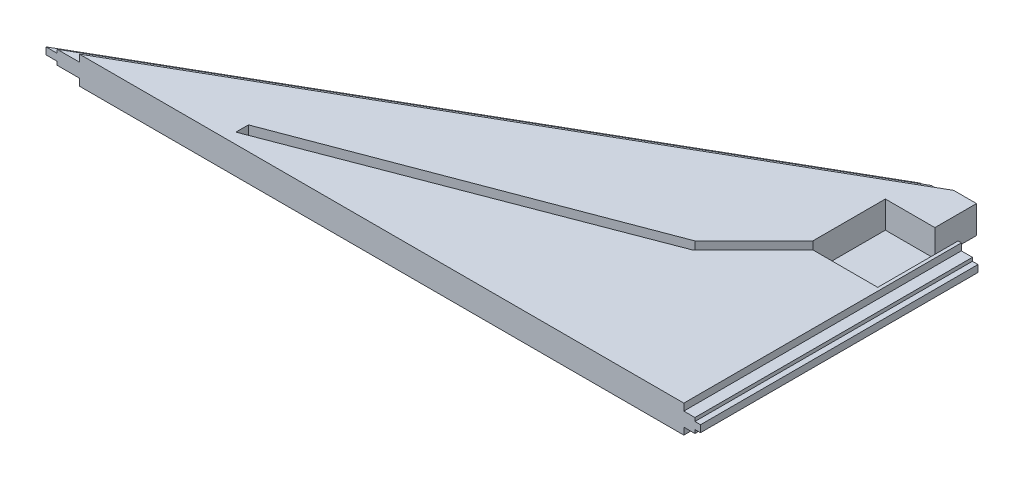
SolidWorks part; units mm, degrees
ref_plane "Front Plane" through (0, 0, 0) normal (0, 0, 1) x (1, 0, 0)
ref_plane "Top Plane" through (0, 0, 0) normal (0, 1, 0) x (1, 0, 0)
ref_plane "Right Plane" through (0, 0, 0) normal (1, 0, 0) x (0, 0, -1)
sketch "Sketch1" plane through (0, 0, 0) normal (0, 1, 0) x (1, 0, 0)
  line L0 (-406.4, 0) -> (0, 0)
  line L1 (0, 0) -> (0, 146.05)
  line L2 (0, 146.05) -> (-152.4, 146.05)
  line L3 (-152.4, 146.05) -> (-406.4, 0)
  dimension "D1" = 406.4
  dimension "D2" = 152.4
  dimension "D3" = 146.05
extrude "Boss-Extrude1" add sketch "Sketch1" along normal blind 6.35 and the other way blind 6.35 contours L3 L0 L1 L2
sketch "Sketch2" plane through (-100.9796, 0, -175.6167) normal (-0.4985, 0, -0.8669) x (-0.8669, 0, 0.4985)
  line L0 (59.3148, 6.35) -> (59.3148, 3.175)
  line L1 (59.3148, -6.35) -> (59.3148, 6.35) construction
  line L2 (59.3148, 3.175) -> (352.3107, 3.175)
  line L3 (352.3107, -6.35) -> (352.3107, 6.35) construction
  line L4 (352.3107, 3.175) -> (352.3107, 6.35)
  line L5 (352.3107, 6.35) -> (59.3148, 6.35)
  line L6 (59.3148, -6.35) -> (59.3148, -3.175)
  line L7 (59.3148, -6.35) -> (352.3107, -6.35)
  line L8 (352.3107, -6.35) -> (352.3107, -3.175)
  line L9 (352.3107, -3.175) -> (59.3148, -3.175)
  dimension "D1" = 3.175
  dimension "D2" = 3.175
extrude "Cut-Extrude1" cut sketch "Sketch2" against normal blind 38.1
sketch "Sketch3" plane through (0, 0, 0) normal (1, 0, 0) x (0, 0, -1)
  line L0 (0, 6.35) -> (0, 3.175)
  line L2 (0, 6.35) -> (146.05, 6.35)
  line L3 (146.05, 6.35) -> (146.05, 3.175)
  line L4 (146.05, -6.35) -> (146.05, 6.35) construction
  line L5 (0, 3.175) -> (146.05, 3.175)
  line L6 (0, -6.35) -> (0, -3.175)
  line L7 (0, -3.175) -> (146.05, -3.175)
  line L8 (146.05, -3.175) -> (146.05, -6.35)
  line L9 (146.05, -6.35) -> (0, -6.35)
  dimension "D1" = 3.175
  dimension "D2" = 3.175
  dimension "D3" = 3.175
  dimension "D4" = 3.175
extrude "Cut-Extrude2" cut sketch "Sketch3" against normal blind 38.1
sketch "Sketch4" plane through (0, 6.35, 0) normal (0, 1, 0) x (1, 0, 0)
  line L0 (-133.4083, 113.0209) -> (-75.9663, 146.05)
  line L1 (-38.1, 146.05) -> (-152.4, 146.05) construction
  line L2 (-75.9663, 146.05) -> (-152.4, 146.05)
  line L3 (-152.4, 146.05) -> (-133.4083, 113.0209)
  line L4 (-329.9663, 0) -> (-133.4083, 113.0209) construction
extrude "Cut-Extrude3" cut sketch "Sketch4" against normal blind 3.175
sketch "Sketch5" plane through (0, -6.35, 0) normal (0, -1, 0) x (1, 0, 0)
  line L0 (-133.4083, -113.0209) -> (-75.9663, -146.05)
  line L1 (-38.1, -146.05) -> (-152.4, -146.05) construction
  line L2 (-75.9663, -146.05) -> (-152.4, -146.05)
  line L3 (-152.4, -146.05) -> (-133.4083, -113.0209)
  line L4 (-329.9663, 0) -> (-133.4083, -113.0209) construction
extrude "Cut-Extrude4" cut sketch "Sketch5" against normal blind 3.175
sketch "Sketch6" plane through (0, 0, -146.05) normal (0, 0, -1) x (-1, 0, 0)
  line L0 (38.1, 6.35) -> (0, 0) construction
  line L1 (0, 0) -> (38.1, -6.35) construction
  line L2 (0, -3.175) -> (0, 3.175) construction
  line L3 (38.622, 3.2182) -> (19.3128, 0) construction
  line L4 (19.3128, 0) -> (38.622, -3.2182) construction
  line L5 (38.1, -3.175) -> (43.18, -3.175)
  line L6 (43.18, -3.175) -> (43.18, -6.35)
  line L7 (38.1, -6.35) -> (75.9663, -6.35) construction
  line L8 (43.18, -6.35) -> (38.1, -6.35)
  line L9 (38.1, 3.175) -> (43.18, 3.175)
  line L10 (43.18, 3.175) -> (43.18, 6.35)
  line L11 (38.1, 6.35) -> (75.9663, 6.35) construction
  line L12 (43.18, 6.35) -> (38.1, 6.35)
  line L13 (38.1, 6.35) -> (0, 6.35)
  line L14 (0, 6.35) -> (0, -6.35)
  line L15 (0, -6.35) -> (38.1, -6.35)
  line L16 (38.1, -3.175) -> (38.1, -1.5875)
  line L22 (38.1, -1.5875) -> (35.56, -1.5875)
  line L23 (35.56, -1.5875) -> (35.56, 1.5875)
  line L24 (35.56, 1.5875) -> (38.1, 1.5875)
  line L25 (38.1, 1.5875) -> (38.1, 3.175)
  line M7 (75.9663, 6.35) -> (38.1, 6.35)
  line M8 (38.1, 6.35) -> (38.1, 3.175)
  line M9 (38.1, 3.175) -> (0, 3.175)
  line M10 (0, 3.175) -> (0, -3.175)
  line M11 (0, -3.175) -> (38.1, -3.175)
  line M12 (38.1, -3.175) -> (38.1, -6.35)
  line M13 (38.1, -6.35) -> (75.9663, -6.35)
  dimension "D2" = 1.5875
  dimension "D1" = 3.175
  dimension "D3" = 5.08
  dimension "D4" = 5.08
  dimension "D5" = 2.54
  dimension "D6" = 3.175
extrude "Cut-Extrude5" cut sketch "Sketch6" against normal blind 157.099 contours L9 L10 M7 M8 | L6 L5 M12 M13 | L4 L3 M11 M9 M10 | L4 L3 region at (-18.4369, 0, -146.05) region at (-40.64, -4.7625, -146.05) region at (-40.64, 4.7625, -146.05)
sketch "Sketch7" plane through (0, -3.175, 0) normal (0, -1, 0) x (1, 0, 0)
  line L0 (-152.4, -146.05) -> (-133.4083, -113.0209) construction
  line L1 (-329.9663, 0) -> (-75.9663, -146.05) construction
  line L2 (-75.9663, -146.05) -> (-329.9663, 0) construction
ref_plane "Plane1" through (-51.4204, 0, 29.5667) normal (-0.8669, 0, 0.4985) x (0.4985, 0, 0.8669)
sketch "Sketch8" plane through (-51.4204, 0, 29.5667) normal (-0.8669, 0, 0.4985) x (0.4985, 0, 0.8669)
  line L0 (-202.5787, 0) -> (-164.4787, 0) construction
  line L1 (-202.5787, -3.175) -> (-202.5787, 3.175) construction
  line L2 (-164.4787, 0) -> (-164.4787, -6.35) construction
  line L3 (-164.4787, -6.35) -> (-202.5787, 0) construction
  line L4 (-202.5787, 0) -> (-164.4787, 6.35) construction
  line L5 (-164.4787, 0) -> (-164.4787, 6.35) construction
  line L6 (-163.9567, -3.2182) -> (-183.2659, 0) construction
  line L7 (-183.2659, 0) -> (-163.9567, 3.2182) construction
  line L8 (-164.4787, 3.175) -> (-159.3987, 3.175)
  line L9 (-159.3987, 3.175) -> (-159.3987, 6.35)
  line L10 (-159.3987, 6.35) -> (-164.4787, 6.35)
  line L11 (-164.4787, -3.175) -> (-159.3987, -3.175)
  line L12 (-159.3987, -3.175) -> (-159.3987, -6.35)
  line L13 (-159.3987, -6.35) -> (-164.4787, -6.35)
  line L14 (-164.4787, 6.35) -> (-202.5787, 6.35)
  line L15 (-202.5787, 6.35) -> (-202.5787, -6.35)
  line L16 (-202.5787, -6.35) -> (-164.4787, -6.35)
  line L17 (-164.4787, -3.175) -> (-164.4787, -1.5875)
  line L23 (-164.4787, -1.5875) -> (-167.0187, -1.5875)
  line L24 (-167.0187, -1.5875) -> (-167.0187, 1.5875)
  line L25 (-167.0187, 1.5875) -> (-164.4787, 1.5875)
  line L26 (-164.4787, 1.5875) -> (-164.4787, 3.175)
  point P7 (-164.4787, -3.175)
  point P11 (-164.4787, 3.175)
  dimension "D5" = 1.5875
  dimension "D1" = 38.1
  dimension "D2" = 6.35
  dimension "D3" = 6.35
  dimension "D6" = 5.08
  dimension "D7" = 3.175
  dimension "D8" = 5.08
  dimension "D9" = 3.175
  dimension "D10" = 38.1
  dimension "D11" = 12.7
  dimension "D12" = 2.54
  dimension "D13" = 3.175
  dimension "D14" = 1.5875
  dimension "D4" = 3.175
extrude "Cut-Extrude6" cut sketch "Sketch8" against normal blind 157.099 and the other way blind 339.217 contours L8 L9 L10 L14 L15 L16 L13 L12 L11 L6 L7 | L7 L6 region at (-142.3615, 0, -128.5917)
sketch "Sketch9" plane through (0, 6.35, 0) normal (0, 1, 0) x (1, 0, 0)
  line L5 (0, 146.05) -> (-50.8, 146.05)
  line L6 (0, 146.05) -> (-152.4, 146.05) construction
  line L7 (-50.8, 146.05) -> (-50.8, 127)
  line L8 (-50.8, 127) -> (0, 127)
  line L9 (0, 0) -> (0, 146.05) construction
  line L10 (0, 146.05) -> (0, 127)
  dimension "D1" = 50.8
  dimension "D2" = 19.05
extrude "Cut-Extrude7" cut sketch "Sketch9" against normal blind 21.59
sketch "Sketch10" plane through (0, 6.35, 0) normal (0, 1, 0) x (1, 0, 0)
  line L0 (-44.68, 127) -> (-44.68, 0) construction
  line L1 (-50.8, 127) -> (-43.18, 127) construction
  line L2 (-319.7751, 0) -> (-43.18, 0) construction
  line L4 (-44.68, 127) -> (-51.765, 127)
  line L5 (-44.68, 127) -> (-44.68, 90.23)
  line L6 (-44.68, 90.23) -> (-51.765, 90.23)
  line L7 (-51.765, 127) -> (-51.765, 90.23)
  line L8 (-51.765, 127) -> (-77.95, 127)
  line L10 (-51.765, 90.23) -> (-77.95, 90.23)
  line L11 (-77.95, 127) -> (-77.95, 90.23)
  line M10 (-43.18, 127) -> (-50.8, 127)
  dimension "D1" = 1.5
  dimension "D2" = 36.77
  dimension "D3" = 7.085
  dimension "D4" = 26.185
extrude "Cut-Extrude9" cut sketch "Sketch10" against normal blind 12.35 contours L8 L11 L10 L7 | L4 L7 L6 L5 M10 region at (-48.2225, 6.35, -108.615) region at (-64.8575, 6.35, -108.615)
sketch "Sketch11" plane through (0, 6.35, 0) normal (0, 1, 0) x (1, 0, 0)
  line L1 (-44.68, 127) -> (-51.765, 127)
  line L2 (-44.68, 127) -> (-44.68, 149.6338)
  line L3 (-44.68, 149.6338) -> (-51.765, 149.6338)
  line L4 (-51.765, 127) -> (-51.765, 149.6338)
  line L5 (-51.765, 127) -> (-55.295, 127)
  line L6 (-51.765, 127) -> (-51.765, 149.6338)
  line L7 (-51.765, 149.6338) -> (-55.295, 149.6338)
  line L8 (-55.295, 127) -> (-55.295, 149.6338)
  line M10 (-77.95, 127) -> (-50.8, 127)
  line M11 (-50.8, 127) -> (-50.8, 146.05)
  line M12 (-50.8, 146.05) -> (-65.7751, 146.05)
  dimension "D1" = 7.085
  dimension "D2" = 3.53
extrude "Cut-Extrude10" cut sketch "Sketch11" against normal through all contours L8 L4 M10 M12 | L4 M10 M11 M12 region at (-51.2825, 6.35, -136.525) region at (-53.53, 6.35, -136.525)
sketch "Sketch12" plane through (0, 6.35, 0) normal (0, 1, 0) x (1, 0, 0)
  line L0 (-77.95, 90.23) -> (-103.35, 64.83)
  line L1 (-44.68, 90.23) -> (-77.95, 90.23) construction
  line L2 (-103.35, 64.83) -> (-253.0681, 7.62)
  line L3 (-319.7751, 0) -> (-43.18, 0) construction
  line L4 (-90.65, 77.53) -> (-88.8539, 75.7339) construction
  line L5 (-90.65, 77.53) -> (-92.4461, 79.3261) construction
  line L6 (-147.0885, 48.1167) -> (-146.1819, 45.744) construction
  line L7 (-147.0885, 48.1167) -> (-147.9952, 50.4894) construction
  line L8 (-88.8539, 75.7339) -> (-101.9371, 62.6508)
  line L9 (-88.8539, 75.7339) -> (-74.3579, 90.23)
  line L10 (-92.4461, 79.3261) -> (-77.95, 93.8221)
  line L11 (-77.95, 127) -> (-77.95, 90.23) construction
  line L12 (-92.4461, 79.3261) -> (-104.9589, 66.8132)
  line L13 (-147.9952, 50.4894) -> (-104.9589, 66.8132)
  line L14 (-146.1819, 45.744) -> (-113.5643, 58.2078)
  line L15 (-146.1819, 45.744) -> (-253.0681, 4.9009)
  line L16 (-113.5643, 58.2078) -> (-101.9371, 62.6508)
  line L17 (-147.9952, 50.4894) -> (-253.0681, 10.6349)
  line L18 (-253.0681, 4.9009) -> (-253.0681, 10.6349)
  line L19 (-44.68, 90.23) -> (-77.95, 90.23) construction
  line L20 (-77.95, 93.8221) -> (-77.95, 90.23)
  line L21 (-104.9589, 66.8132) -> (-101.9371, 62.6508) construction
  line M14 (-44.68, 90.23) -> (-77.95, 90.23)
  line M15 (-77.95, 90.23) -> (-77.95, 127)
  dimension "D1" = 135
  dimension "D2" = 25.4
  dimension "D3" = 25.4
  dimension "D4" = 7.62
  dimension "D5" = 90
  dimension "D6" = 90
  dimension "D7" = 2.54
  dimension "D8" = 2.54
  dimension "D9" = 2.54
  dimension "D10" = 2.54
  dimension "D11" = 90
extrude "Cut-Extrude11" cut sketch "Sketch12" against normal blind 5.08 contours L18 L2 L0 L10 L12 L13 L17 M15 | L18 L15 L14 L16 L8 L9 L0 L2 M14 region at (-76.1539, 6.35, -90.032) region at (-92.0302, 6.35, -78.9102)
sketch "Sketch13" plane through (-44.68, 0, 0) normal (-1, 0, 0) x (0, 0, 1)
  line L0 (-127, 6.35) -> (-106.9, 6.35) construction
  line L1 (-127, 6.35) -> (-90.23, 6.35) construction
  line L4 (-106.9, 6.35) -> (-102.9, 6.35) construction
  line L8 (-109.106, -2.325) -> (-99.106, -2.325)
  line L9 (-109.106, -2.325) -> (-109.106, 2.675)
  line L10 (-109.106, 2.675) -> (-99.106, 2.675)
  line L11 (-99.106, -2.325) -> (-99.106, 2.675)
  line L12 (-109.106, -2.325) -> (-99.106, 2.675) construction
  line L13 (-109.106, 2.675) -> (-99.106, -2.325) construction
  point P14 (-104.106, 0.175)
  dimension "D1" = 20.1
  dimension "D2" = 2.794
  dimension "D3" = 5
  dimension "D4" = 10
  dimension "D5" = 8.876
extrude "Cut-Extrude13" cut sketch "Sketch13" against normal blind 3.5 contours L8 L11 L10 L9 region at (-44.68, 0.175, -104.106)
sketch "Sketch15" plane through (0, 6.35, 0) normal (0, 1, 0) x (1, 0, 0)
  line L0 (-77.95, 90.23) -> (-45.45, 90.23) construction
  line L1 (-44.68, 90.23) -> (-74.3579, 90.23) construction
  dimension "D1" = 32.5
